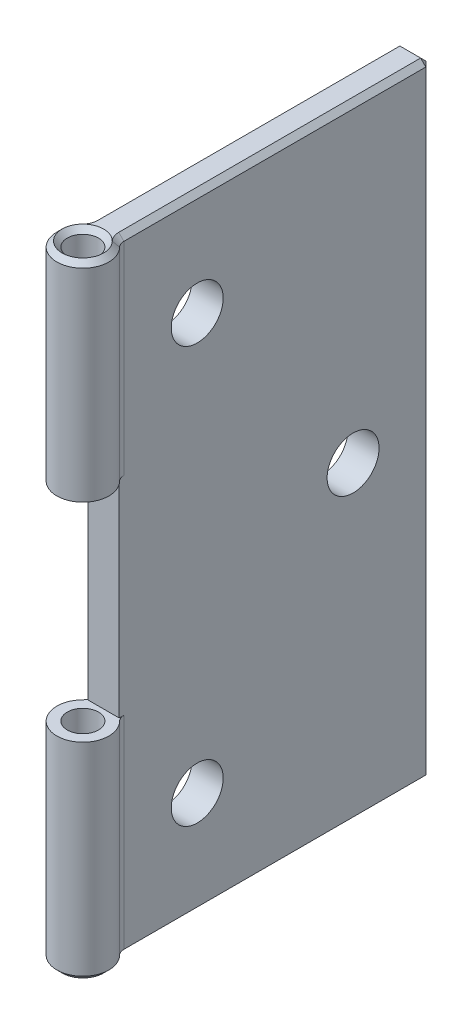
SolidWorks part; units mm, degrees
material "Brass"
ref_plane "Front Plane" through (0, 0, 0) normal (0, 0, 1) x (1, 0, 0)
ref_plane "Top Plane" through (0, 0, 0) normal (0, 1, 0) x (1, 0, 0)
ref_plane "Right Plane" through (0, 0, 0) normal (1, 0, 0) x (0, 0, -1)
sketch "Sketch1" plane through (0, 0, 0) normal (1, 0, 0) x (0, 0, -1)
  line L1 (15, -30) -> (-15, -30)
  line L2 (15, -30) -> (15, 30)
  line L3 (15, 30) -> (-15, 30)
  line L4 (-15, -30) -> (-15, 30)
  line L5 (15, -30) -> (-15, 30) construction
  line L6 (15, 30) -> (-15, -30) construction
  circle A0 centre (-7.5, 20) radius 2.5
  circle A1 centre (7.5, 0) radius 2.5
  circle A2 centre (-7.5, -20) radius 2.5
  point P0 (0, 0)
  point P12 (15, 0)
  dimension "D5" = 5
  dimension "D1" = 60
  dimension "D2" = 30
  dimension "D3" = 7.5
  dimension "D4" = 10
  dimension "D6" = 7.5
  dimension "D7" = 10
extrude "Boss-Extrude1" add sketch "Sketch1" along normal mid plane 3
sketch "Sketch3" plane through (0, 30, 0) normal (0, 1, 0) x (1, 0, 0)
  line L0 (-1.5, -15) -> (1.5, -15)
  arc A0 (-1.5, -15) -> (1.5, -15) centre (0, -17) ccw
  circle A1 centre (0, -17) radius 1.5
  dimension "D1" = 3
  dimension "D2" = 5
extrude "Boss-Extrude2" add sketch "Sketch3" against normal blind 20
mirror "Mirror1" about plane through (0, 0, 0) normal (0, 1, 0) of "Boss-Extrude2"
fillet "Fillet1" radius 1 4 edges at (-1.5, -20, 15) (-1.5, 20, 15) (1.5, -20, 15) (1.5, 20, 15)
chamfer "Chamfer1" distance 0.5 angle 45 16 edges at (0, -30, 18.5) (0, 30, 18.5) (1.5742, -30, 14.9285) (1.5, -30, -0.2247) (0, -30, 19.5) (-1.5742, -30, 14.9285) (-1.5, -30, -0.2247) (0, -30, -15) (1.5, 0, -15) (-1.5, 0, -15) (0, 30, -15) (1.5, 30, -0.2247) (1.5742, 30, 14.9285) (0, 30, 19.5) (-1.5742, 30, 14.9285) (-1.5, 30, -0.2247)
